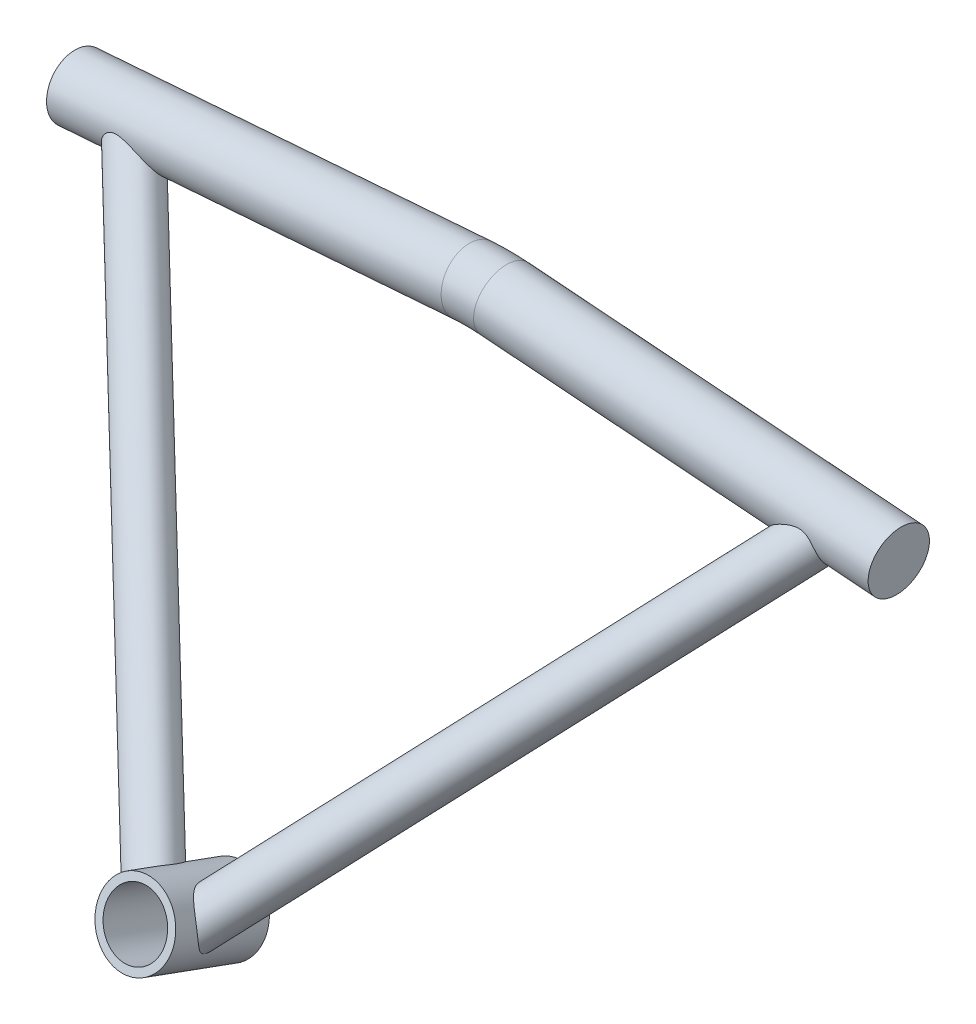
SolidWorks part; units mm, degrees
material "AISI 4130 Steel, normalized at 870C"
ref_plane "Front Plane" through (0, 0, 0) normal (0, 0, 1) x (1, 0, 0)
ref_plane "Top Plane" through (0, 0, 0) normal (0, 1, 0) x (1, 0, 0)
ref_plane "Right Plane" through (0, 0, 0) normal (1, 0, 0) x (0, 0, -1)
sketch "Sketch3" plane through (0, 0, 0) normal (0, 1, 0) x (1, 0, 0)
  line L0 (-5.08, -6.35) -> (5.08, -6.35) construction
  line L2 (0, -88.2205) -> (0, 88.2205) construction
  line L3 (5.08, 0) -> (-5.08, 0) construction
  dimension "D1" = 5.08
  dimension "D2" = 10.16
  dimension "D3" = 6.35
  dimension "D4" = 10.16
  dimension "D5" = 5.08
ref_plane "Plane1" through (0, 3.1441, 3.6169) normal (0, 0.6561, 0.7547) x (1, 0, 0)
ref_plane "Plane3" through (0, 0, 0) normal (0, 0.342, 0.9397) x (-1, 0, 0)
sketch "Sketch1" plane through (0, 0, 0) normal (0, 0.342, 0.9397) x (1, 0, 0)
  circle A0 centre (0, 0) radius 15.875
  dimension "D1" = 31.75
extrude "Boss-Extrude1" add sketch "Sketch1" along normal mid plane 41.402 contours A0
sketch "Sketch4" plane through (0, 3.1441, 3.6169) normal (0, 0.6561, 0.7547) x (1, 0, 0)
  line L0 (-5.08, -4.166) -> (-143.484, 193.4954)
  line L2 (0, -90.5202) -> (0, 90.5202) construction
  dimension "D2" = 35
  dimension "D3" = 241.3
sweep "Sweep1" add path "Sketch4" circular profile diameter 19.05 parameters "D3"=19.05
sketch "Sketch15" plane through (0, 3.1441, 3.6169) normal (0, 0.6561, 0.7547) x (1, 0, 0)
  line L0 (5.08, -4.166) -> (143.484, 193.4954)
  line L1 (0, -90.5202) -> (0, 90.5202) construction
  dimension "D1" = 241.3
  dimension "D2" = 35
sweep "Sweep2" add path "Sketch15" circular profile diameter 19.05 parameters "D3"=19.05
sketch "Sketch36" plane through (-138.1179, 148.8686, -129.4095) normal (-0.5736, 0.6182, -0.5374) x (0.8191, 0.4394, -0.3687)
  circle A0 centre (-6.5024, -4.8578) radius 7.9375
  dimension "D1" = 15.875
extrude "Cut-Extrude2" cut sketch "Sketch36" against normal up to surface (251.5099 mm away) up to face at (15.2328, -2.8486, 5.2417)
sketch "Sketch37" plane through (138.1179, 148.8686, -129.4095) normal (0.5736, 0.6182, -0.5374) x (0.8191, -0.4394, 0.3687)
  circle A0 centre (6.5024, -4.8578) radius 7.9375
  dimension "D1" = 15.875
extrude "Cut-Extrude3" cut sketch "Sketch37" against normal up to surface (226.8376 mm away) up to face at (10.6472, -5.7729, 18.5671)
sketch "Sketch77" plane through (0, 7.0802, 19.4526) normal (0, 0.342, 0.9397) x (1, 0, 0)
  circle A1 centre (0, 0) radius 15.875
extrude "Boss-Extrude2" add sketch "Sketch77" against normal up to surface (41.402 mm away) up to face at (0, -21.9978, -14.023)
sketch "Sketch2" plane through (0, -7.0802, -19.4526) normal (0, -0.342, -0.9397) x (-1, 0, 0)
  circle A0 centre (0, 0) radius 12.7
  dimension "D1" = 25.4
extrude "Cut-Extrude1" cut sketch "Sketch2" against normal up to next
ref_plane "Plane2" through (0, 0, -127) normal (0, 0, 1) x (1, 0, 0)
sketch "Sketch40" plane through (-106.934, 0, -127) normal (0, 0, 1) x (1, 0, 0)
  line L2 (106.934, -85.9333) -> (106.934, 85.9333) construction
  line L3 (100.2024, 162.3048) -> (-63.6638, 149.8608)
  line L4 (113.6656, 162.3048) -> (277.5318, 149.8608)
  arc A0 (100.2024, 162.3048) -> (113.6656, 162.3048) centre (106.934, 73.66) cw
  point P0 (106.934, 162.56)
  point P7 (106.934, 162.56)
  dimension "D1" = 164.338
  dimension "D3" = 88.9
  dimension "D2" = 164.338
  dimension "D4" = 4.75
sweep "Sweep3" add path "Sketch40" circular profile diameter 25.4 parameters "D3"=25.4
